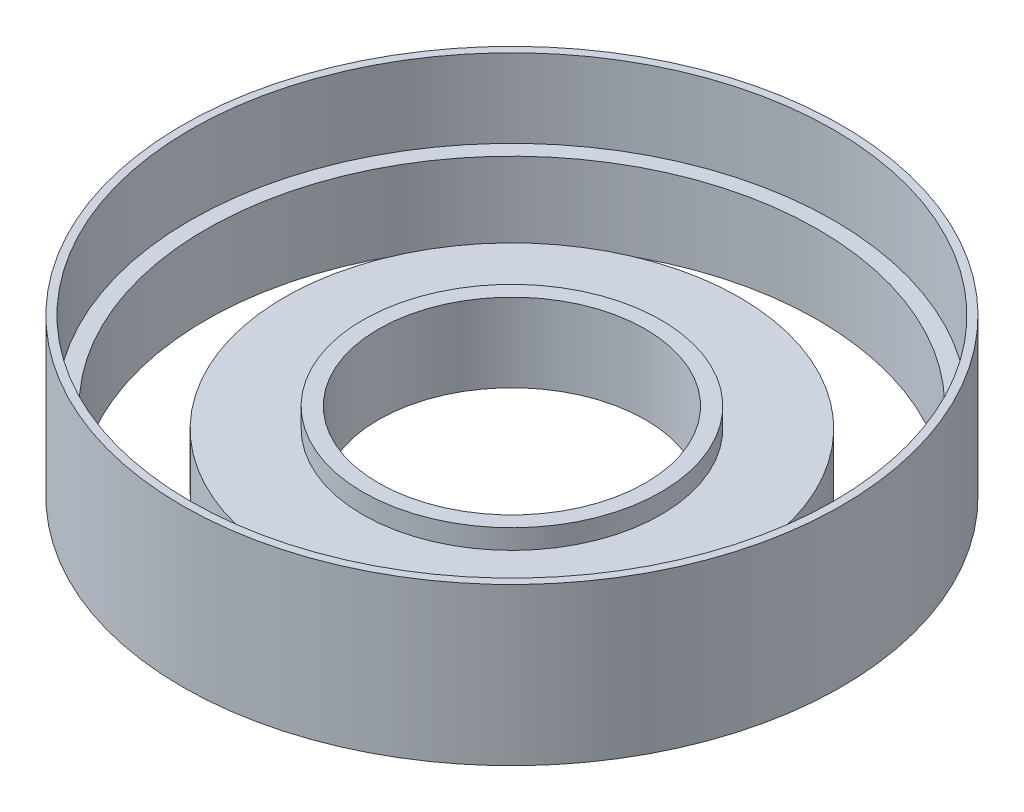
SolidWorks part; units mm, degrees
other "Markup1"
sketch "Sketch2" plane through (-42, 20, 42) normal (-0.06, 0.9253, 0.3744) x (0.8401, 0.2494, -0.4817)
ref_plane "Front" through (0, 0, 0) normal (0, 0, 1) x (1, 0, 0)
ref_plane "Top" through (0, 0, 0) normal (0, 1, 0) x (1, 0, 0)
ref_plane "Right" through (0, 0, 0) normal (1, 0, 0) x (0, 0, -1)
sketch "Sketch1" plane through (0, 0, 0) normal (0, 1, 0) x (1, 0, 0)
  line L0 (0, 0) -> (0, 7) construction
  circle A0 centre (0, 0) radius 17
  circle A1 centre (0, 0) radius 19
  circle A2 centre (0, 0) radius 29
  circle A3 centre (0, 0) radius 39
  circle A4 centre (0, 0) radius 41
  circle A5 centre (0, 0) radius 42
  point P17 (0, 42)
  dimension "D1" = 34
  dimension "D7" = 7
  dimension "D2" = 2
  dimension "D3" = 10
  dimension "D4" = 10
  dimension "D5" = 2
  dimension "D6" = 1
extrude "Boss-Extrude1" add sketch "Sketch1" along normal blind 20 contours A4 | A5
extrude "Boss-Extrude2" add sketch "Sketch1<3>" along normal blind 10 contours A4 A3 | A1 A0 region at (-18.4626, 0, 0) region at (-39.8403, 0, 0)
sketch "Sketch1<3>" plane through (0, 0, 0) normal (0, 1, 0) x (1, 0, 0) same geometry as "Sketch1"
extrude "Boss-Extrude3" add sketch "Sketch1<4>" along normal blind 7.5 contours A2 A1 region at (-28.1798, 0, 0)
sketch "Sketch1<4>" plane through (0, 0, 0) normal (0, 1, 0) x (1, 0, 0) same geometry as "Sketch1"
